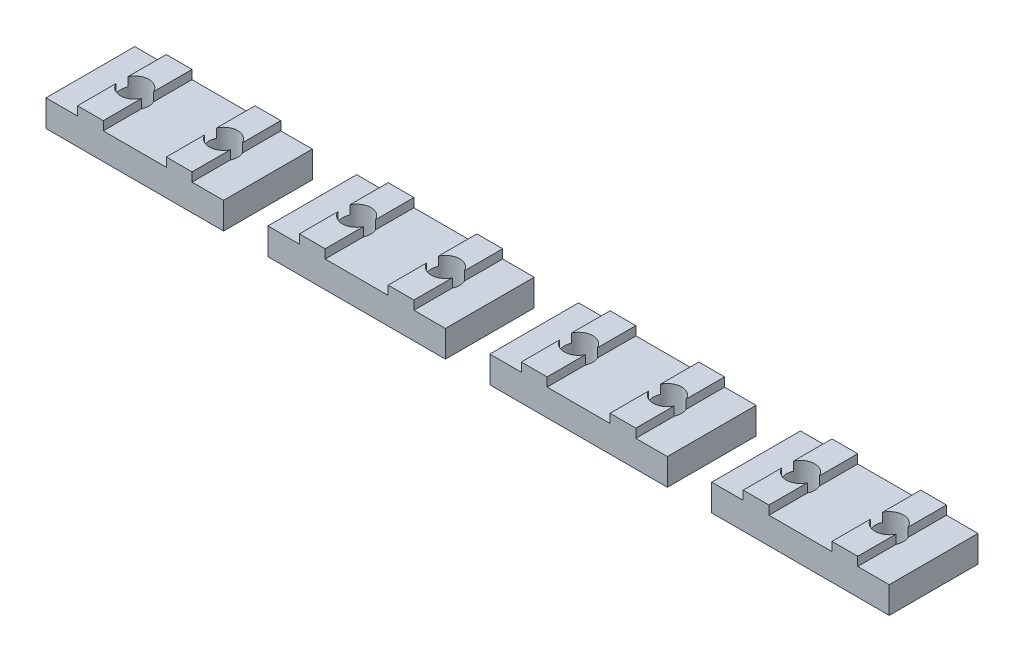
SolidWorks part; units mm, degrees
ref_plane "Front Plane" through (0, 0, 0) normal (0, 0, 1) x (1, 0, 0)
ref_plane "Top Plane" through (0, 0, 0) normal (0, 1, 0) x (1, 0, 0)
ref_plane "Right Plane" through (0, 0, 0) normal (1, 0, 0) x (0, 0, -1)
sketch "Esquisse1" plane through (0, 0, 0) normal (0, 0, 1) x (1, 0, 0)
  line L0 (-5, 0) -> (-5, 3)
  line L1 (-5, 3) -> (-1.45, 3)
  line L2 (-1.45, 3) -> (-1.45, 4)
  line L3 (-1.45, 4) -> (1.45, 4)
  line L4 (1.45, 4) -> (1.45, 3)
  line L5 (1.45, 3) -> (5, 3)
  line L6 (5, 3) -> (5, 0)
  line L7 (5, 0) -> (-5, 0)
  point P11 (0, 0)
  dimension "D1" = 10
  dimension "D2" = 3
  dimension "D3" = 1
  dimension "D4" = 2.9
  dimension "D5" = 3.55
extrude "Main" add sketch "Esquisse1" along normal blind 10
sketch "Esquisse2" plane through (0, 4, 0) normal (0, 1, 0) x (1, 0, 0)
  line L0 (0, -2.2) -> (0, 2.2) construction
  line L2 (-1.45, -10) -> (-5, -10) construction
  circle A1 centre (0, -5) radius 1.6
  dimension "D2" = 5
  dimension "D1" = 3.2
extrude "TopHole" cut sketch "Esquisse2" against normal through all
ref_axis "Axe1" through (-5.5, 0, 0) along (1, 0, 0)
pattern_linear "Répétition linéaire1" count 2 spacing 10 along (-1, 0, 0) of "TopHole", "Main"
pattern_linear "Répétition linéaire2" count 4 spacing 25 along (-1, 0, 0) of "Répétition linéaire1"
